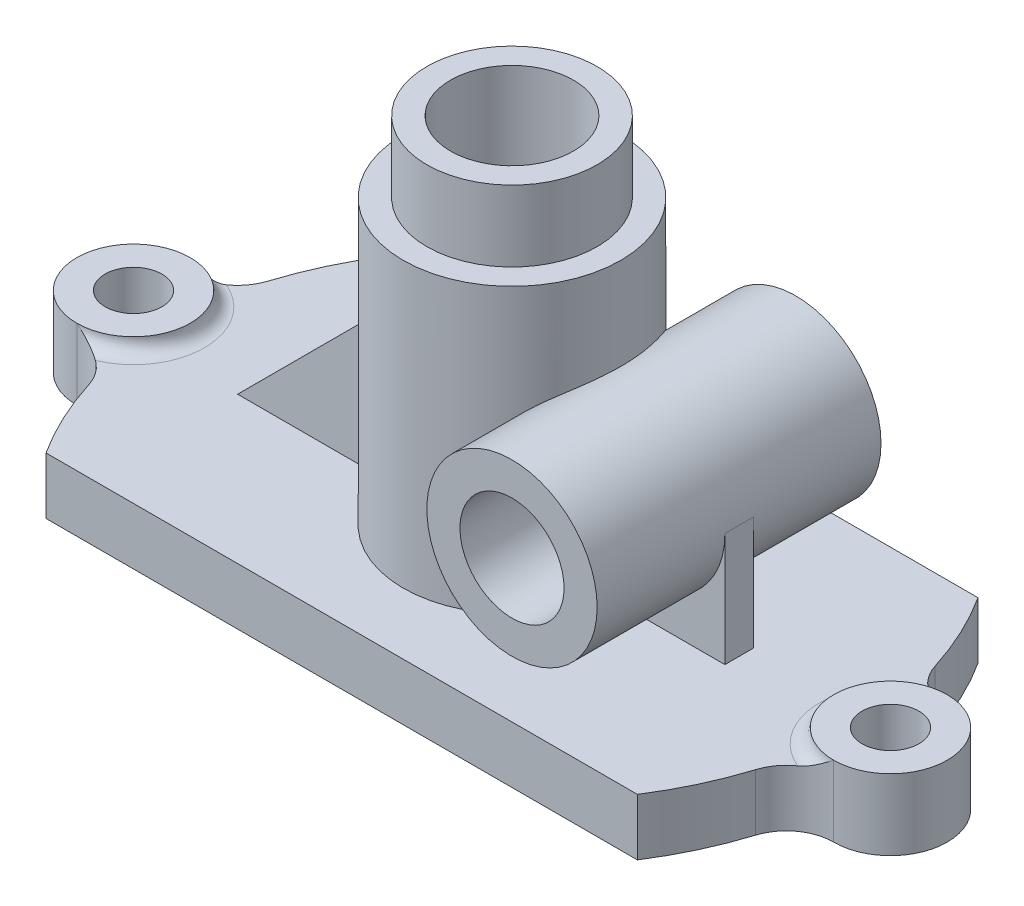
SolidWorks part; units mm, degrees
ref_plane "Front Plane" through (0, 0, 0) normal (0, 0, 1) x (1, 0, 0)
ref_plane "Top Plane" through (0, 0, 0) normal (0, 1, 0) x (1, 0, 0)
ref_plane "Right Plane" through (0, 0, 0) normal (1, 0, 0) x (0, 0, -1)
sketch "Sketch1" plane through (0, 0, 0) normal (0, 1, 0) x (1, 0, 0)
  line L0 (-80, 0) -> (80, 0) construction
  circle A0 centre (-80, 0) radius 12
  circle A1 centre (-80, 0) radius 6
  circle A2 centre (80, 0) radius 12
  circle A3 centre (80, 0) radius 6
  point P3 (0, 0)
  dimension "D2" = 12
  dimension "D3" = 24
  dimension "D4" = 12
  dimension "D5" = 24
  dimension "D1" = 80
extrude "Boss-Extrude1" add sketch "Sketch1" along normal blind 15
sketch "Sketch2" plane through (0, 0, 0) normal (0, 1, 0) x (1, 0, 0)
  line L0 (-80, 0) -> (80, 0) construction
  line L1 (-62.5, 36) -> (62.5, 36)
  line L2 (-62.5, -36) -> (62.5, -36)
  line L3 (-80, -12) -> (-80, 12) construction
  line L4 (80, 12) -> (80, -12) construction
  arc A0 (-70.4624, 18.9944) -> (-80, 12) centre (-80, 22) cw
  arc A1 (-70.4624, -18.9944) -> (-80, -12) centre (-80, -22) ccw
  arc A2 (-70.4624, 18.9944) -> (-62.5, 36) centre (-2.7452, -2.3453) cw
  circle A3 centre (-80, 0) radius 12 construction
  arc A4 (-70.4624, -18.9944) -> (-62.5, -36) centre (-2.7452, 2.3453) ccw
  arc A5 (80, 12) -> (70.4624, 18.9944) centre (80, 22) cw
  circle A6 centre (80, 0) radius 12 construction
  arc A7 (62.5, 36) -> (70.4624, 18.9944) centre (2.7452, -2.3453) cw
  arc A8 (80, -12) -> (70.4624, -18.9944) centre (80, -22) ccw
  arc A9 (70.4624, -18.9944) -> (62.5, -36) centre (2.7452, 2.3453) cw
  arc A10 (-80, 12) -> (-80, -12) centre (-80, 0) cw
  arc A11 (80, -12) -> (80, 12) centre (80, 0) cw
  dimension "D7" = 10
  dimension "D8" = 71
  dimension "D9" = 10
  dimension "D10" = 71
  dimension "D12" = 71
  dimension "D1" = 62.5
  dimension "D2" = 36
  dimension "D3" = 36
  dimension "D4" = 62.5
  dimension "D5" = 62.5
  dimension "D6" = 62.5
extrude "Boss-Extrude2" add sketch "Sketch2" along normal blind 12 contours A8 A11 A5 A7 L1 A2 A0 A10 A1 A4 L2 A9 region at (0, 0, 0)
ref_plane "Plane1" through (0, 12, 0) normal (0, 1, 0) x (1, 0, 0)
sketch "Sketch5" plane through (0, 12, 0) normal (0, 1, 0) x (1, 0, 0)
  circle A0 centre (0, 0) radius 23
  dimension "D1" = 46
extrude "Boss-Extrude3" add sketch "Sketch5" along normal blind 60
sketch "Sketch6" plane through (0, 72, 0) normal (0, 1, 0) x (1, 0, 0)
  circle A0 centre (0, 0) radius 18
  dimension "D1" = 36
extrude "Boss-Extrude4" add sketch "Sketch6" along normal blind 15
sketch "Sketch7" plane through (0, 87, 0) normal (0, 1, 0) x (1, 0, 0)
  circle A0 centre (0, 0) radius 13
  dimension "D1" = 26
extrude "Cut-Extrude1" cut sketch "Sketch7" against normal blind 107 contours A0
sketch "Sketch8" plane through (0, 0, 0) normal (0, 0, 1) x (1, 0, 0)
  line L0 (80, 0) -> (92, 0) construction
  line L1 (0, 0) -> (0, 87) construction
  line L2 (13, 87) -> (-13, 87) construction
  circle A0 centre (30, 36) radius 18
  circle A1 centre (30, 36) radius 11
  dimension "D1" = 22
  dimension "D2" = 36
  dimension "D3" = 36
  dimension "D4" = 30
extrude "Boss-Extrude5" add sketch "Sketch8" along normal mid plane 60
fillet "Fillet1" radius 3 1 edges at (-68, 12, 0)
fillet "Fillet2" radius 3 1 edges at (68, 12, 0)
sketch "Sketch9" plane through (0, 87, 0) normal (0, 1, 0) x (1, 0, 0)
  circle A0 centre (0, 0) radius 13
  dimension "D1" = 26
extrude "Cut-Extrude2" cut sketch "Sketch9" against normal blind 103
sketch "Sketch10" plane through (0, 0, 0) normal (0, 0, 1) x (1, 0, 0)
  line L0 (48, 36) -> (48, 12)
  line L1 (-62.5, 12) -> (62.5, 12) construction
  circle A0 centre (30, 36) radius 18 construction
  dimension "D1" = 48
rib "Rib1" sketch "Sketch10" sketch "Sketch10" thickness 6 extrusion direction parallel to sketch draft on no parameters "D1"=6
sketch "Sketch11" plane through (0, 0, 0) normal (0, 0, 1) x (1, 0, 0)
  line L0 (-23, 42) -> (-53, 12)
  line L1 (-62.5, 12) -> (62.5, 12) construction
  line L2 (-23, 72) -> (-23, 12) construction
  point P6 (0, 0)
  dimension "D1" = 30
  dimension "D2" = 30
rib "Rib2" sketch "Sketch11" sketch "Sketch11" thickness 10 extrusion direction parallel to sketch draft on no parameters "D1"=10
